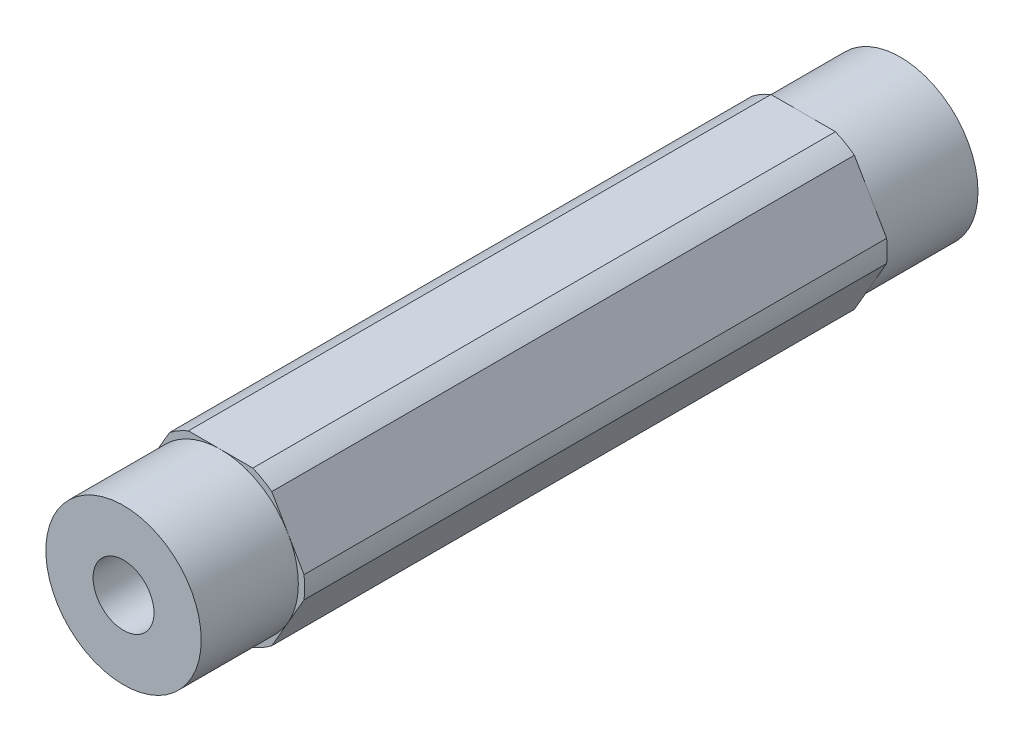
SolidWorks part; units mm, degrees
ref_plane "Front Plane" through (0, 0, 0) normal (0, 0, 1) x (1, 0, 0)
ref_plane "Top Plane" through (0, 0, 0) normal (0, 1, 0) x (1, 0, 0)
ref_plane "Right Plane" through (0, 0, 0) normal (1, 0, 0) x (0, 0, -1)
sketch "Sketch1" plane through (0, 0, 0) normal (0, 0, 1) x (1, 0, 0)
  line L1 (-3.6662, 6.35) -> (-7.3323, 0)
  line L2 (-7.3323, 0) -> (-3.6662, -6.35)
  line L3 (-3.6662, -6.35) -> (3.6662, -6.35)
  line L4 (3.6662, -6.35) -> (7.3323, 0)
  line L5 (7.3323, 0) -> (3.6662, 6.35)
  line L6 (3.6662, 6.35) -> (-3.6662, 6.35)
  circle A0 centre (0, 0) radius 6.875
  circle A1 centre (0, 0) radius 6.35 construction
  circle A2 centre (0, 0) radius 2.4892
  point P12 (0, 6.35)
  dimension "D1" = 12.7
  dimension "D2" = 13.75
  dimension "D3" = 4.9784
extrude "Boss-Extrude1" add sketch "Sketch1" along normal mid plane 63.5 contours L5 A0 L6 L1 L2 L3 L4 region at (-3.3439, 5.7918, 0)
sketch "Sketch2" plane through (0, 0, 31.75) normal (0, 0, 1) x (1, 0, 0)
  circle A0 centre (0, 0) radius 6.35
  line M2 (6.8168, 0.893) -> (4.1818, 5.457)
  arc M3 (4.1818, 5.457) -> (2.635, 6.35) centre (0, 0) ccw
  line M4 (2.635, 6.35) -> (-2.635, 6.35)
  arc M5 (-2.635, 6.35) -> (-4.1818, 5.457) centre (0, 0) ccw
  line M6 (-4.1818, 5.457) -> (-6.8168, 0.893)
  arc M7 (-6.8168, 0.893) -> (-6.8168, -0.893) centre (0, 0) ccw
  line M8 (-6.8168, -0.893) -> (-4.1818, -5.457)
  arc M9 (-4.1818, -5.457) -> (-2.635, -6.35) centre (0, 0) ccw
  line M10 (-2.635, -6.35) -> (2.635, -6.35)
  arc M11 (2.635, -6.35) -> (4.1818, -5.457) centre (0, 0) ccw
  line M12 (4.1818, -5.457) -> (6.8168, -0.893)
  arc M13 (6.8168, -0.893) -> (6.8168, 0.893) centre (0, 0) ccw
  dimension "D1" = 12.7
extrude "Cut-Extrude2" cut sketch "Sketch2" against normal blind 7.9375 contours A0 M4 M5 M6 | A0 M2 M3 M4 | A0 M12 M13 M2 | A0 M10 M11 M12 | A0 M8 M9 M10 | A0 M6 M7 M8 region at (6.4637, 0, 31.75) region at (3.2318, 5.5977, 31.75) region at (3.2318, -5.5977, 31.75) region at (-3.2318, 5.5977, 31.75) region at (-3.2318, -5.5977, 31.75) region at (-6.4637, 0, 31.75)
mirror "Mirror1" about plane through (0, 0, 0) normal (0, 0, 1) of "Cut-Extrude2"
equation "\"D2@Sketch1\"=13.75mm"
